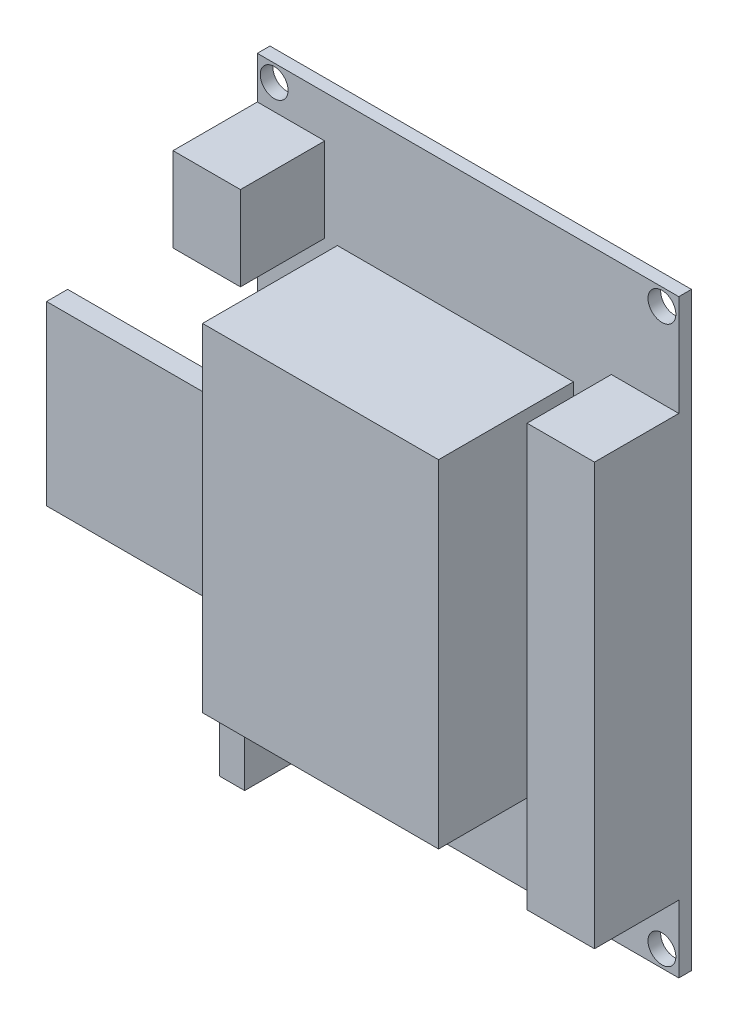
SolidWorks part; units mm, degrees
ref_plane "Front Plane" through (0, 0, 0) normal (0, 0, 1) x (1, 0, 0)
ref_plane "Top Plane" through (0, 0, 0) normal (0, 1, 0) x (1, 0, 0)
ref_plane "Right Plane" through (0, 0, 0) normal (1, 0, 0) x (0, 0, -1)
sketch "Sketch1" plane through (0, 0, 0) normal (0, 0, 1) x (1, 0, 0)
  line L0 (0, 35) -> (50, 35) construction
  line L1 (0, 0) -> (50, 0)
  line L2 (0, 0) -> (0, 70)
  line L3 (0, 70) -> (50, 70)
  line L4 (50, 0) -> (50, 70)
  line L5 (25, 0) -> (25, 70) construction
  line L7 (4, 43) -> (7, 43)
  line L8 (4, 43) -> (4, 2)
  line L9 (4, 2) -> (7, 2)
  line L10 (7, 43) -> (7, 2)
  line L11 (42, 58) -> (50, 58)
  line L12 (42, 58) -> (42, 8)
  line L13 (42, 8) -> (50, 8)
  line L14 (50, 58) -> (50, 8)
  line L15 (7, 43) -> (-14, 43)
  line L16 (7, 43) -> (7, 22)
  line L17 (7, 22) -> (-14, 22)
  line L18 (-14, 43) -> (-14, 22)
  line L19 (9.5, 55) -> (37.5, 55)
  line L20 (9.5, 55) -> (9.5, 15)
  line L21 (9.5, 15) -> (37.5, 15)
  line L22 (37.5, 55) -> (37.5, 15)
  line L23 (0, 65) -> (8, 65)
  line L24 (0, 65) -> (0, 55)
  line L25 (0, 55) -> (8, 55)
  line L26 (8, 65) -> (8, 55)
  circle A1 centre (48, 2) radius 1.65
  circle A2 centre (48, 68) radius 1.65
  circle A3 centre (2, 2) radius 1.65
  circle A4 centre (2, 68) radius 1.65
  point P33 (37.5, 35)
  dimension "D3" = 3.3
  dimension "D4" = 66
  dimension "D1" = 50
  dimension "D2" = 70
  dimension "D5" = 46
  dimension "D6" = 50
  dimension "D7" = 8
  dimension "D8" = 8
  dimension "D9" = 28
  dimension "D10" = 40
  dimension "D11" = 4.5
  dimension "D12" = 3
  dimension "D13" = 3
  dimension "D14" = 41
  dimension "D15" = 4
  dimension "D16" = 21
  dimension "D17" = 21
  dimension "D18" = 2
  dimension "D19" = 5
  dimension "D20" = 10
  dimension "D21" = 8
extrude "Main-Protoboard" add sketch "Sketch1" along normal blind 1.5 contours L8 L17 L2 L1 L4 L13 L12 L11 L3 L15 L7 L10 L9 A4 A2 A1 A3 | L12 L13 L4 L11 | L17 L8 L15 L2 | L10 L9 L8 L7 | L24 L23 L26 L25 | L20 L19 L22 L21 region at (0.8602, 11, 0) region at (2, 32.5, 0) region at (46, 33, 0)
extrude "Screw-Terminals" add sketch "Sketch1<3>" along normal blind 10 from surface contours L12 L13 L4 L11 | L24 L23 L26 L25 region at (46, 33, 0) starting at face at (25, 35, 1.5)
sketch "Sketch1<3>" plane through (0, 0, 0) normal (0, 0, 1) x (1, 0, 0) same geometry as "Sketch1"
extrude "MCU" add sketch "Sketch1<5>" along normal blind 16 from surface contours L22 L19 L20 L21 region at (23.5, 35, 0) starting at face at (25, 42.6667, 1.5)
sketch "Sketch1<5>" plane through (0, 0, 0) normal (0, 0, 1) x (1, 0, 0) same geometry as "Sketch1"
extrude "Dupont-Connectors" add sketch "Sketch1<6>" along normal blind 10 contours L10 L9 L8 L7
sketch "Sketch1<6>" plane through (0, 0, 0) normal (0, 0, 1) x (1, 0, 0) same geometry as "Sketch1"
extrude "Can-Transceiver" add sketch "Sketch1<7>" along normal blind 2.5 from surface contours L15 L18 L17 L2 | L17 L8 L15 L2 | L17 L10 L7 L8 region at (-7, 32.5, 0) region at (2, 32.5, 0) region at (5.5, 32.5, 0) starting at face at (5.5, 22.5, 10)
sketch "Sketch1<7>" plane through (0, 0, 0) normal (0, 0, 1) x (1, 0, 0) same geometry as "Sketch1"
extrude "Wire-Clearance" add sketch "Sketch1<8>" against normal blind 6 contours L22 L19 L20 L21 region at (23.5, 35, 0)
sketch "Sketch1<8>" plane through (0, 0, 0) normal (0, 0, 1) x (1, 0, 0) same geometry as "Sketch1"
